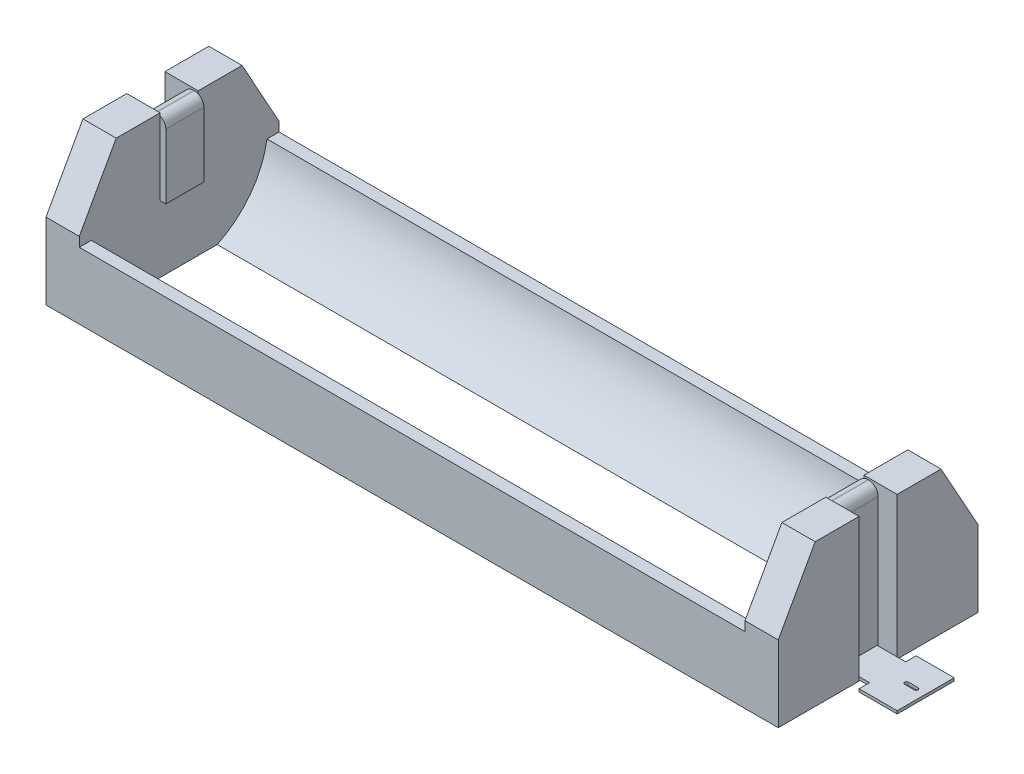
SolidWorks part; units mm, degrees
ref_plane "Płaszczyzna przednia" through (0, 0, 0) normal (0, 0, 1) x (1, 0, 0)
ref_plane "Płaszczyzna górna" through (0, 0, 0) normal (0, 1, 0) x (1, 0, 0)
ref_plane "Płaszczyzna prawa" through (0, 0, 0) normal (1, 0, 0) x (0, 0, -1)
sketch "Szkic1" plane through (0, 0, 0) normal (0, 1, 0) x (1, 0, 0)
  line L0 (0, 16.6009) -> (0, -20.6468) construction
  line L1 (-38.5, -10.5) -> (38.5, -10.5)
  line L2 (-38.5, -10.5) -> (-38.5, 10.5)
  line L3 (-38.5, 10.5) -> (38.5, 10.5)
  line L4 (38.5, -10.5) -> (38.5, 10.5)
  line L5 (-38.5, -10.5) -> (38.5, 10.5) construction
  line L6 (-38.5, 10.5) -> (38.5, -10.5) construction
  line L7 (-38.5, 10.5) -> (-35, 10.5)
  line L8 (-38.5, 10.5) -> (-38.5, -10.5)
  line L9 (-38.5, -10.5) -> (-35, -10.5)
  line L10 (-35, 10.5) -> (-35, -10.5)
  line L11 (38.5, -10.5) -> (35, -10.5)
  line L12 (35, 10.5) -> (35, -10.5)
  line L13 (38.5, 10.5) -> (35, 10.5)
  line L14 (38.5, 10.5) -> (38.5, -10.5)
  line L15 (38.5, -2) -> (38.5, 2)
  line L16 (-35, -4) -> (35, -4)
  line L17 (-35, -4) -> (-35, 4)
  line L18 (-35, 4) -> (35, 4)
  line L19 (35, -4) -> (35, 4)
  line L20 (-38.5, -2) -> (-36.5, -2)
  line L21 (-38.5, -2) -> (-38.5, 2)
  line L22 (-38.5, 2) -> (-36.5, 2)
  line L23 (-36.5, -2) -> (-36.5, 2)
  line L24 (38.5, -2) -> (36.5, -2)
  line L25 (36.5, -2) -> (36.5, 2)
  line L26 (38.5, 2) -> (36.5, 2)
  point P0 (0, 0)
  point P20 (-37.5, -2)
  dimension "D1" = 21
  dimension "D2" = 77
  dimension "D3" = 3.5
  dimension "D4" = 8
  dimension "D5" = 4
  dimension "D6" = 2
  dimension "D7" = 4
  dimension "D8" = 2
extrude "Dodanie-wyciągnięcie1" add sketch "Szkic1" along normal blind 15 contours L10 L3 L2 L1 | L3 L12 L1 L4 region at (-38.2871, 0, 6.25) region at (35.2129, 0, 7.25)
extrude "Dodanie-wyciągnięcie2" add sketch "Szkic1<3>" along normal blind 7 contours L16 L10 L1 L12 | L10 L18 L12 L3 region at (0, 0, 7.25) region at (0, 0, -7.25)
sketch "Szkic1<3>" plane through (0, 0, 0) normal (0, 1, 0) x (1, 0, 0) same geometry as "Szkic1"
sketch "Szkic2" plane through (-35, 0, 0) normal (1, 0, 0) x (0, 0, -1)
  circle A0 centre (0, 8.4512) radius 9.35
  dimension "D1" = 18.7
extrude "Wytnij-wyciągnięcie1" cut sketch "Szkic2" along normal up to surface (70 mm away) up to face at (35, 7.25, 0)
sketch "Szkic3" plane through (0, 0, 0) normal (0, 1, 0) x (1, 0, 0)
  line L0 (-36.5, 1.9) -> (-39.5, 1.9)
  line L1 (-36.5, -2) -> (-36.5, 2) construction
  line L2 (-39.5, 1.9) -> (-39.5, 3)
  line L3 (-39.5, 3) -> (-43.5, 3)
  line L4 (-43.5, 3) -> (-43.5, -3)
  line L5 (-43.5, 0) -> (-36.5, 0)
  line L6 (-36.5, -1.9) -> (-36.5, 1.9)
  line L7 (-42.5, 0) -> (-41.5, 0) construction
  line L8 (-42.5, 0.2) -> (-41.5, 0.2)
  line L9 (-42.5, -0.2) -> (-41.5, -0.2)
  line L10 (-38.5, 2) -> (-38.5, 10.5) construction
  line L11 (51.321, 0) -> (-60.425, 0) construction
  line L12 (0, -36.5173) -> (0, 27.4151) construction
  line L13 (-39.5, -3) -> (-43.5, -3)
  line L14 (-39.5, -1.9) -> (-39.5, -3)
  line L15 (-36.5, -1.9) -> (-39.5, -1.9)
  line L16 (42.5, 0) -> (41.5, 0) construction
  line L17 (42.5, 0.2) -> (41.5, 0.2)
  line L18 (42.5, -0.2) -> (41.5, -0.2)
  line L19 (36.5, -1.9) -> (39.5, -1.9)
  line L20 (39.5, -1.9) -> (39.5, -3)
  line L21 (39.5, -3) -> (43.5, -3)
  line L22 (36.5, -1.9) -> (36.5, 1.9)
  line L23 (43.5, 0) -> (36.5, 0)
  line L24 (43.5, 3) -> (43.5, -3)
  line L25 (39.5, 3) -> (43.5, 3)
  line L26 (39.5, 1.9) -> (39.5, 3)
  line L27 (36.5, 1.9) -> (39.5, 1.9)
  arc A0 (-42.5, 0.2) -> (-42.5, -0.2) centre (-42.5, 0) ccw
  arc A1 (-41.5, -0.2) -> (-41.5, 0.2) centre (-41.5, 0) ccw
  arc A2 (42.5, 0.2) -> (42.5, -0.2) centre (42.5, 0) cw
  arc A3 (41.5, -0.2) -> (41.5, 0.2) centre (41.5, 0) cw
  point P10 (-42, 0)
  point P28 (42, 0)
  dimension "D2" = 0.2
  dimension "D1" = 1
  dimension "D3" = 1
  dimension "D4" = 5
  dimension "D5" = 4
  dimension "D6" = 3
  dimension "D7" = 1.9
extrude "Dodanie-wyciągnięcie3" add sketch "Szkic3" along normal blind 0.3 contours A1 L5 L6 L0 L2 L3 L4 A0 L8 | A1 L9 A0 L5 L4 L13 L14 L15 L6 | L23 A3 L17 A2 L24 L25 L26 L27 L22 | L18 A3 L23 L22 L19 L20 L21 L24 A2 region at (-40.3484, 0, -1.3414) region at (-40.3484, 0, 1.3414) region at (40.3484, 0, -1.3414) region at (40.3484, 0, 1.3414)
chamfer "Sfazowanie1" distance 7 angle 29 4 edges at (36.75, 15, 10.5) (36.75, 15, -10.5) (-36.75, 15, -10.5) (-36.75, 15, 10.5) tangent propagation no first distance on face at (0, 9.25, 10.5) first distance on face at (0, 9.25, -10.5)
sketch "Szkic4" plane through (-35, 0, 0) normal (1, 0, 0) x (0, 0, -1)
  line L0 (2, 15) -> (2, 0) construction
  line L1 (-2, 15) -> (2, 15)
  line L2 (-2, 15) -> (-2, 7)
  line L3 (-2, 7) -> (2, 7)
  line L4 (2, 15) -> (2, 7)
  line L6 (-2, 15) -> (2, 15)
  line L7 (-2, 15) -> (-2, 14.8)
  line L8 (-2, 14.8) -> (2, 14.8)
  line L9 (2, 15) -> (2, 14.8)
  line M6 (6.6198, 15) -> (-6.6198, 15)
  dimension "D1" = 0.2
  dimension "D2" = 8
extrude "Wytnij-wyciągnięcie2" cut sketch "Szkic4" against normal up to next contours L2 L8 L4 M6 region at (-35, 14.9, 0)
extrude "Dodanie-wyciągnięcie4" add sketch "Szkic4<3>" along normal blind 0.6 contours L8 L2 L3 L4 region at (-35, 10.9, 0)
sketch "Szkic4<3>" plane through (-35, 0, 0) normal (1, 0, 0) x (0, 0, -1) same geometry as "Szkic4"
mirror "Lustro1" about plane through (0, 0, 0) normal (1, 0, 0) of "Wytnij-wyciągnięcie2", "Dodanie-wyciągnięcie4"
fillet "Zaokrąglenie1" radius 1 4 edges at (36.5, 14.8, 0) (34.4, 14.8, 0) (-34.4, 14.8, 0) (-36.5, 14.8, 0)
equation "\"D5@Szkic1\"=\"D4@Szkic1\"/2"
equation "\"D8@Szkic1\"=\"D7@Szkic1\"/2"
